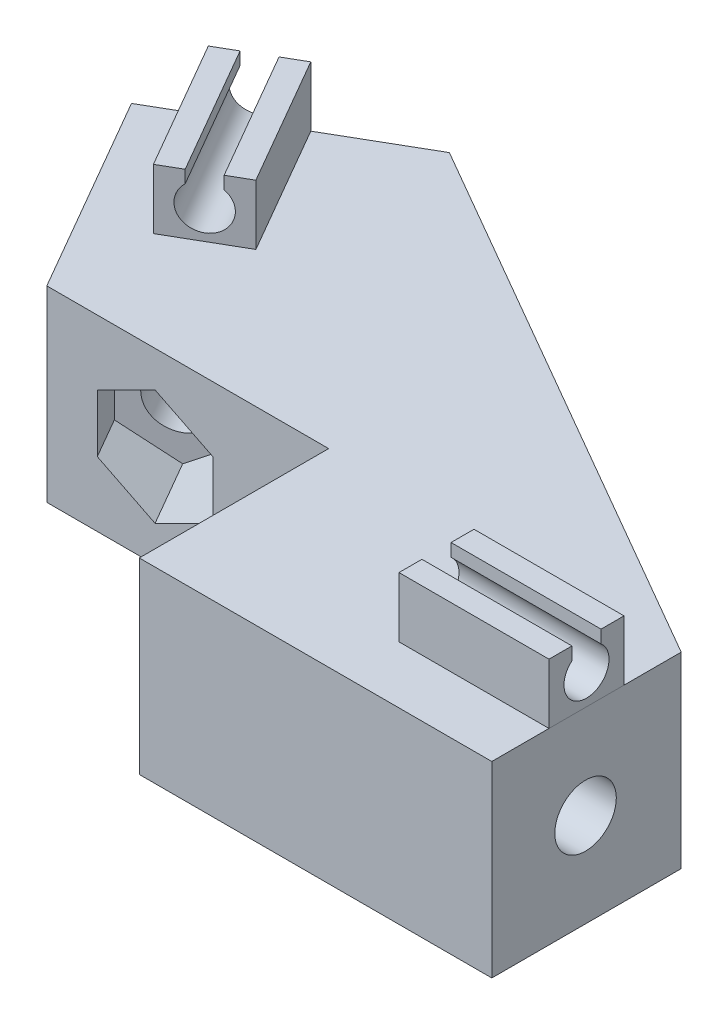
SolidWorks part; units mm, degrees
ref_plane "Спереди" through (0, 0, 0) normal (0, 0, 1) x (1, 0, 0)
ref_plane "Сверху" through (0, 0, 0) normal (0, 1, 0) x (1, 0, 0)
ref_plane "Справа" through (0, 0, 0) normal (1, 0, 0) x (0, 0, -1)
sketch "Sketch1" plane through (0, 0, 0) normal (0, 1, 0) x (1, 0, 0)
  line L0 (-32.9441, 45.4045) -> (-2.9441, -6.5571)
  line L1 (-2.9441, -6.5571) -> (67.0559, -6.5571)
  line L2 (67.0559, -6.5571) -> (67.0559, 18.4429)
  line L3 (67.0559, 18.4429) -> (11.4897, 18.4429)
  line L4 (11.4897, 18.4429) -> (-11.2935, 57.9045)
  line L5 (-11.2935, 57.9045) -> (-32.9441, 45.4045)
  dimension "D1" = 120
  dimension "D2" = 25
  dimension "D3" = 70
  dimension "D4" = 60
extrude "Boss-Extrude1" add sketch "Sketch1" along normal blind 25
sketch "Sketch2" plane through (67.0559, 0, 0) normal (1, 0, 0) x (0, 0, -1)
  line L0 (18.4429, 12.5) -> (-6.5571, 12.5) construction
  line L1 (18.4429, 25) -> (18.4429, 0) construction
  line L2 (-6.5571, 25) -> (-6.5571, 0) construction
  circle A0 centre (5.9429, 12.5) radius 4.1
  dimension "D1" = 8.2
extrude "Cut-Extrude1" cut sketch "Sketch2" against normal through all
sketch "Sketch3" plane through (-27.8967, 0, -48.3186) normal (-0.5, 0, -0.866) x (-0.866, 0, 0.5)
  line L0 (-6.6718, 0) -> (-6.6718, 25) construction
  line L1 (-19.1718, 0) -> (5.8282, 0) construction
  line L2 (-19.1718, 25) -> (5.8282, 25) construction
  circle A0 centre (-6.6718, 12.5) radius 4.1
  dimension "D1" = 8.2
extrude "Cut-Extrude2" cut sketch "Sketch3" against normal through all
sketch "Sketch5" plane through (-27.8967, 0, -48.3186) normal (-0.5, 0, -0.866) x (-0.866, 0, 0.5)
  line L1 (-13.3402, 16.35) -> (-13.3402, 8.65)
  line L2 (-13.3402, 8.65) -> (-6.6718, 4.8)
  line L3 (-6.6718, 4.8) -> (-0.0034, 8.65)
  line L4 (-0.0034, 8.65) -> (-0.0034, 16.35)
  line L5 (-0.0034, 16.35) -> (-6.6718, 20.2)
  line L6 (-6.6718, 20.2) -> (-13.3402, 16.35)
  line L7 (-19.1718, 25) -> (-19.1718, 0) construction
  circle A0 centre (-6.6718, 12.5) radius 7.7 construction
  dimension "D1" = 15.4
extrude "Cut-Extrude4" cut sketch "Sketch5" against normal through all from offset 28 offset against normal yes
chamfer "Chamfer1" distance 56 angle 30 1 edges at (11.4897, 12.5, -18.4429) first distance on face at (39.2728, 12.5, -18.4429)
sketch "Sketch6" plane through (0, 0, 0) normal (0, -1, 0) x (1, 0, 0)
  line L0 (20.0559, 6.5571) -> (20.0559, -18.6934)
  line L1 (-2.9441, 6.5571) -> (67.0559, 6.5571) construction
  line L2 (20.0559, -18.6934) -> (-17.5224, -18.6934)
  line L3 (-32.9441, -45.4045) -> (-2.9441, 6.5571) construction
  line L4 (20.0559, 6.5571) -> (-2.9441, 6.5571)
  line L5 (-2.9441, 6.5571) -> (-17.5224, -18.6934)
  line L6 (67.0559, 6.5571) -> (67.0559, -18.6934) construction
  dimension "D1" = 23
extrude "Cut-Extrude5" cut sketch "Sketch6" against normal through all
sketch "Sketch7" plane through (-27.8967, 0, -48.3186) normal (-0.5, 0, -0.866) x (-0.866, 0, 0.5)
  line L0 (-6.6718, 16.6) -> (-6.6718, 39.225) construction
  line L2 (-25.1957, 25) -> (5.8282, 25) construction
  line L3 (-1.6718, 33) -> (-11.6718, 33) construction
  line L4 (-1.6718, 33) -> (-1.6718, 25)
  line L5 (-1.6718, 25) -> (-11.6718, 25)
  line L6 (-11.6718, 33) -> (-11.6718, 25)
  line L7 (-1.6718, 33) -> (-11.6718, 25) construction
  line L8 (-1.6718, 25) -> (-11.6718, 33) construction
  line L9 (-11.6718, 33) -> (-8.5718, 33)
  line L10 (-8.5718, 33) -> (-8.5718, 31.3216)
  line L11 (-8.5718, 31.3216) -> (-4.7718, 31.3216) construction
  line L13 (-4.7718, 31.3216) -> (-4.7718, 33)
  line L14 (-4.7718, 33) -> (-1.6718, 33)
  circle A1 centre (-6.6718, 12.5) radius 4.1 construction
  circle A2 centre (-6.6718, 29) radius 3 construction
  arc A3 (-8.5718, 31.3216) -> (-4.7718, 31.3216) centre (-6.6718, 29) ccw
  point P4 (-6.6718, 29)
  dimension "D3" = 6
  dimension "D1" = 8
  dimension "D2" = 10
  dimension "D4" = 3.8
extrude "Boss-Extrude2" add sketch "Sketch7" against normal blind 20
sketch "Sketch8" plane through (67.0559, 0, 0) normal (1, 0, 0) x (0, 0, -1)
  line L0 (6.0682, 25) -> (6.0682, 46.5452) construction
  line L2 (-6.5571, 25) -> (18.6934, 25) construction
  line L3 (1.0682, 33) -> (4.1278, 33)
  line L4 (1.0682, 33) -> (11.0682, 33) construction
  line L5 (1.0682, 33) -> (1.0682, 25)
  line L6 (1.0682, 25) -> (11.0682, 25)
  line L7 (11.0682, 33) -> (11.0682, 25)
  line L8 (1.0682, 33) -> (11.0682, 25) construction
  line L9 (1.0682, 25) -> (11.0682, 33) construction
  line L10 (4.1278, 33) -> (4.1278, 31.288)
  line L11 (4.1278, 31.288) -> (8.0085, 31.288) construction
  line L12 (8.0085, 31.288) -> (8.0085, 33)
  line L13 (8.0085, 33) -> (11.0682, 33)
  circle A0 centre (6.0682, 29) radius 3 construction
  arc A1 (4.1278, 31.288) -> (8.0085, 31.288) centre (6.0682, 29) ccw
  point P4 (6.0682, 29)
  dimension "D3" = 10
  dimension "D1" = 6
  dimension "D2" = 8
extrude "Boss-Extrude3" add sketch "Sketch8" against normal blind 20 separate body
